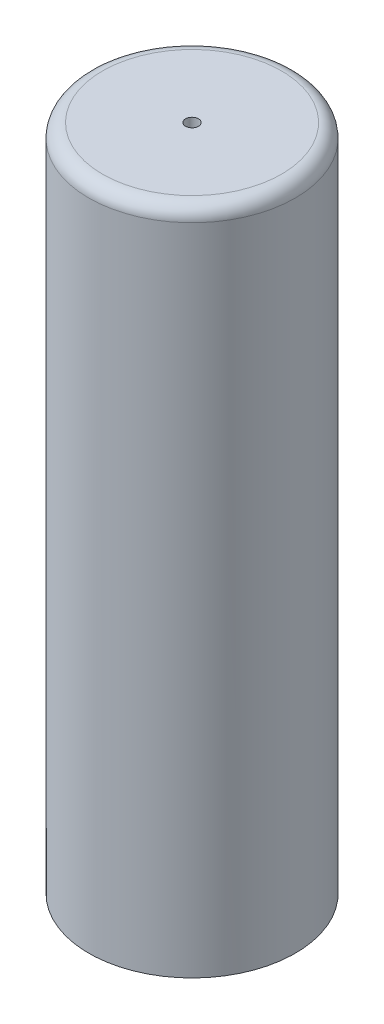
SolidWorks part; units mm, degrees
ref_plane "Front Plane" through (0, 0, 0) normal (0, 0, 1) x (1, 0, 0)
ref_plane "Top Plane" through (0, 0, 0) normal (0, 1, 0) x (1, 0, 0)
ref_plane "Right Plane" through (0, 0, 0) normal (1, 0, 0) x (0, 0, -1)
sketch "Sketch1" plane through (0, 0, 0) normal (0, 1, 0) x (1, 0, 0)
  circle A0 centre (0, 0) radius 19.05
  dimension "D1" = 38.1
extrude "Boss-Extrude1" add sketch "Sketch1" along normal mid plane 120.65
sketch "Sketch3" plane through (0, 60.325, 0) normal (0, 1, 0) x (1, 0, 0)
  circle A0 centre (0, 0) radius 18.05
  circle A1 centre (0, 0) radius 19.05 construction
  dimension "D1" = 1
extrude "Cut-Extrude1" cut sketch "Sketch3" against normal through all
sketch "Sketch4" plane through (0, 60.325, 0) normal (0, 1, 0) x (1, 0, 0)
  circle A0 centre (0, 0) radius 19.05
extrude "Boss-Extrude2" add sketch "Sketch4" along normal blind 2.54
fillet "Fillet1" radius 2.54 1 edges at (0, 62.865, 19.05)
sketch "Sketch5" plane through (0, 62.865, 0) normal (0, 1, 0) x (1, 0, 0)
  circle A0 centre (0, 0) radius 1.2
  dimension "D1" = 2.4
extrude "Cut-Extrude2" cut sketch "Sketch5" against normal through all
